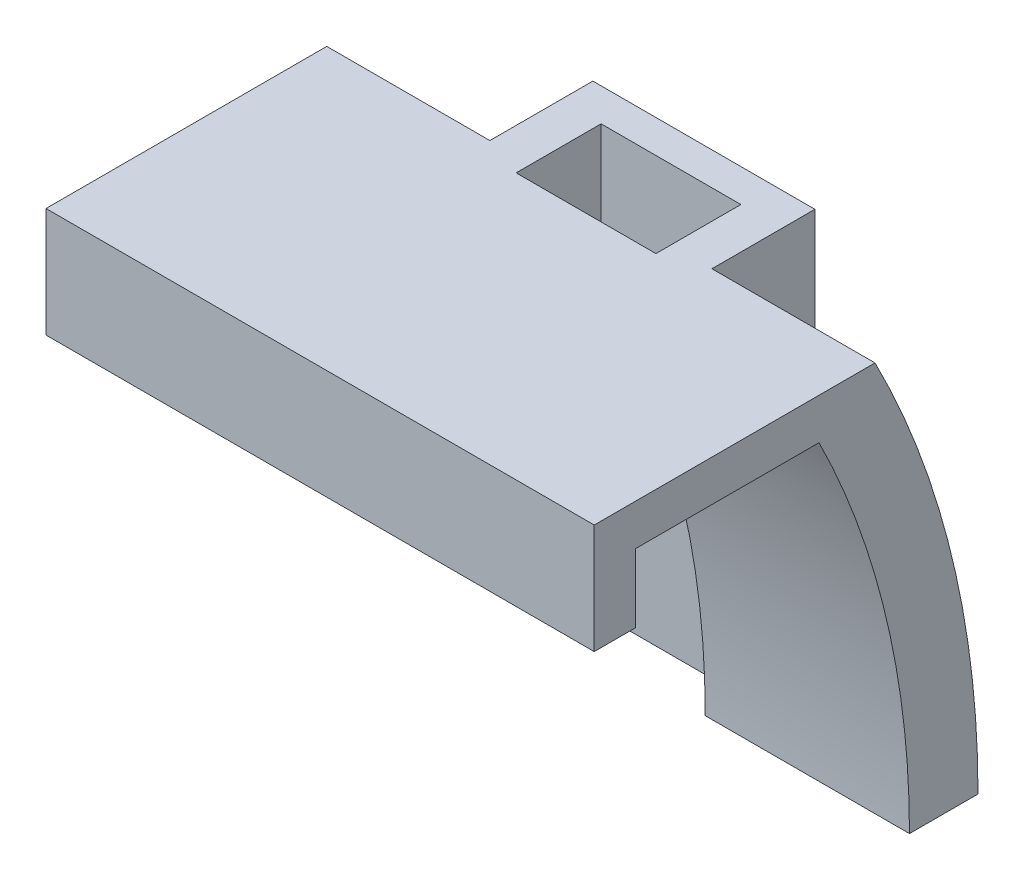
SolidWorks part; units mm, degrees
ref_plane "Front Plane" through (0, 0, 0) normal (0, 0, 1) x (1, 0, 0)
ref_plane "Top Plane" through (0, 0, 0) normal (0, 1, 0) x (1, 0, 0)
ref_plane "Right Plane" through (0, 0, 0) normal (1, 0, 0) x (0, 0, -1)
sketch "Sketch2" plane through (0, 0, 0) normal (1, 0, 0) x (0, 0, -1)
  line L1 (25.4, -35.56) -> (0, -35.56) construction
  line L6 (0, 0) -> (0, -6.35)
  line L7 (0, -6.35) -> (-3.81, -6.35)
  line L8 (-3.81, -6.35) -> (-3.81, 3.81)
  line L9 (-3.81, 3.81) -> (22.2056, 3.81)
  line L10 (25.4, -35.56) -> (31.75, -35.56)
  line L11 (0, 0) -> (17.018, 0)
  arc A0 (25.4, -35.56) -> (17.018, 0) centre (-54.2213, -35.56) ccw
  arc A1 (31.75, -35.56) -> (22.2056, 3.81) centre (-54.2213, -35.56) ccw
  arc A2 (31.75, -35.56) -> (22.6995, 2.836) centre (-54.2213, -35.56) ccw construction
  dimension "D1" = 17.018
  dimension "D2" = 35.56
  dimension "D3" = 8.382
  dimension "D4" = 3.81
  dimension "D5" = 6.35
  dimension "D6" = 6.35
  dimension "D7" = 10.16
extrude "Boss-Extrude1" add sketch "Sketch2" along normal mid plane 50.8
sketch "Sketch3" plane through (0, 0, 0) normal (1, 0, 0) x (0, 0, -1)
  line L0 (31.75, -35.56) -> (31.75, 3.81)
  line L1 (22.2056, 3.81) -> (31.75, 3.81)
  line L2 (22.2056, 3.81) -> (31.75, -35.56)
extrude "Boss-Extrude2" add sketch "Sketch3" along normal mid plane 20.574
ref_plane "Plane1" through (0, 3.81, 0) normal (0, 1, 0) x (1, 0, 0)
sketch "Sketch4" plane through (0, 3.81, 0) normal (0, 1, 0) x (1, 0, 0)
  line L1 (-6.477, 28.702) -> (6.477, 28.702)
  line L2 (-6.477, 28.702) -> (-6.477, 20.828)
  line L3 (-6.477, 20.828) -> (6.477, 20.828)
  line L4 (6.477, 28.702) -> (6.477, 20.828)
  dimension "D1" = 7.874
  dimension "D2" = 12.954
  dimension "D3" = 6.477
  dimension "D4" = 3.048
extrude "Cut-Extrude1" cut sketch "Sketch4" against normal through all
